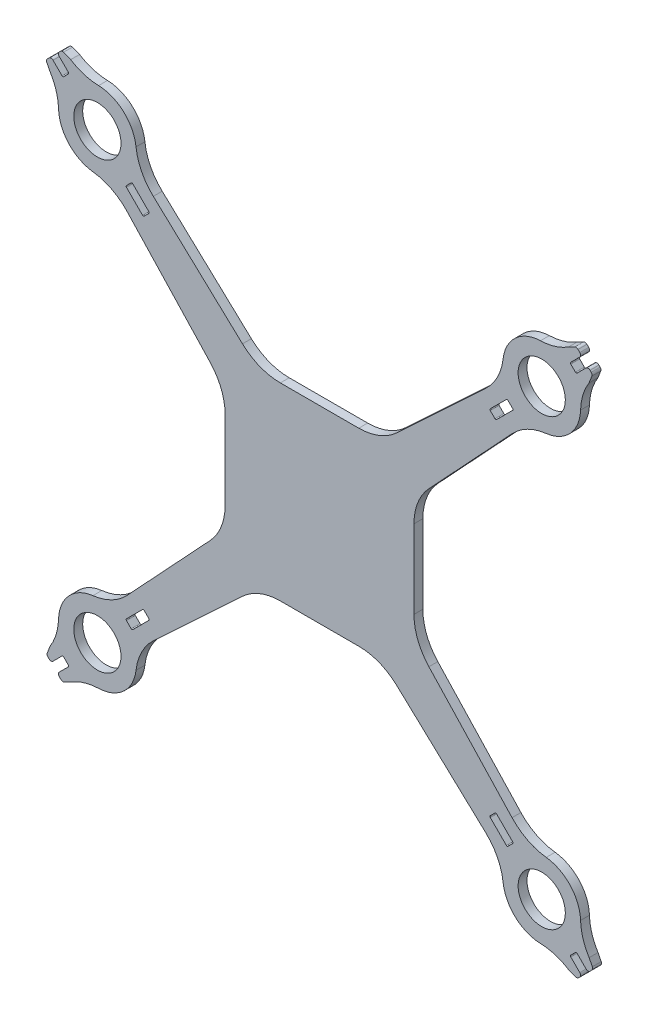
SolidWorks part; units mm, degrees
ref_plane "Front Plane" through (0, 0, 0) normal (0, 0, 1) x (1, 0, 0)
ref_plane "Top Plane" through (0, 0, 0) normal (0, 1, 0) x (1, 0, 0)
ref_plane "Right Plane" through (0, 0, 0) normal (1, 0, 0) x (0, 0, -1)
sketch "Sketch1" plane through (0, 0, 0) normal (0, 0, 1) x (1, 0, 0)
  line L2 (11, 17) -> (33.3431, 37.8353)
  line L3 (37.8353, 33.3431) -> (17, 11)
  line L13 (-24.6528, -24.6528) -> (24.4251, 24.4251) construction
  line L14 (-31.6177, 0) -> (30.5216, 0) construction
  line L22 (0, 54.5816) -> (0, -52.9231) construction
  line L23 (11, 17) -> (42.8566, 46.7068) construction
  line L24 (17, 11) -> (49.3174, 45.6562) construction
  line L25 (42.6238, 46.4897) -> (44.8179, 48.5357)
  line L26 (46.4897, 42.6238) -> (48.5357, 44.8179)
  line L27 (-34.2792, 50) -> (50, 50) construction
  line L28 (50, 50) -> (50, -17.5369) construction
  line L29 (44.8179, 48.5357) -> (46.2756, 49.2808)
  line L30 (11, 17) -> (0, 17)
  line L31 (0, 17) -> (0, 0)
  line L32 (0, 0) -> (17, 0)
  line L33 (17, 0) -> (17, 11)
  line L35 (30.5955, 31.7269) -> (33.7775, 34.9088)
  line L36 (34.9088, 33.7775) -> (31.7269, 30.5955)
  line L37 (46.2756, 49.2808) -> (47.2125, 48.3439)
  line L38 (49.1412, 46.4151) -> (48.5357, 44.8179)
  line L39 (30.5955, 31.7269) -> (31.7269, 30.5955)
  line L41 (33.7775, 34.9088) -> (34.9088, 33.7775)
  line L42 (47.2125, 48.3439) -> (45.0912, 46.2225)
  line L43 (45.0912, 46.2225) -> (46.2225, 45.0912)
  line L44 (46.2225, 45.0912) -> (48.3439, 47.2125)
  line L45 (48.3439, 47.2125) -> (49.1412, 46.4151)
  arc A0 (33.3431, 37.8353) -> (37.8353, 33.3431) centre (40, 40) cw
  circle A6 centre (40, 40) radius 4.25
  circle A9 centre (40, 40) radius 8 construction
  point P31 (45.6569, 45.6569)
  point P60 (0, -20)
  dimension "D1" = 7
  dimension "D2" = 4.5
  dimension "D3" = 1.6
  dimension "D4" = 40
  dimension "D13" = 8.5
  dimension "D6" = 16
  dimension "D18" = 1.6
  dimension "D5" = 45
  dimension "D7" = 47
  dimension "D8" = 47
  dimension "D9" = 47
  dimension "D10" = 47
  dimension "D11" = 50
  dimension "D12" = 11
  dimension "D14" = 11
  dimension "D15" = 17
  dimension "D16" = 17
  dimension "D17" = 3
  dimension "D19" = 3
extrude "Boss-Extrude1" add sketch "Sketch1" along normal blind 1.6 contours L3 A0 L2 A6 | A0 L26 region at (19.208, 19.208, 0) region at (43.7844, 47.4445, 0)
fillet "Fillet1" radius 10 2 edges at (11, 17, 0.8) (17, 11, 0.8)
fillet "Fillet2" radius 0.2 6 edges at (34.9088, 33.7775, 0.8) (31.7269, 30.5955, 0.8) (30.5955, 31.7269, 0.8) (33.7775, 34.9088, 0.8) (46.2225, 45.0912, 0.8) (45.0912, 46.2225, 0.8)
fillet "Fillet3" radius 0.5 4 edges at (49.1412, 46.4151, 0.8) (46.2756, 49.2808, 0.8) (47.2125, 48.3439, 0.8) (48.3439, 47.2125, 0.8)
fillet "Fillet4" radius 10 4 edges at (37.8353, 33.3431, 0.8) (33.3431, 37.8353, 0.8) (42.6238, 46.4897, 0.8) (46.4897, 42.6238, 0.8)
pattern_circular "CirPattern1" count 4 over 360 about axis through (0, 0, 1.6) along (0, 0, -1) of "Boss-Extrude1", "Fillet1", "Fillet3", "Fillet2", "Fillet4"
